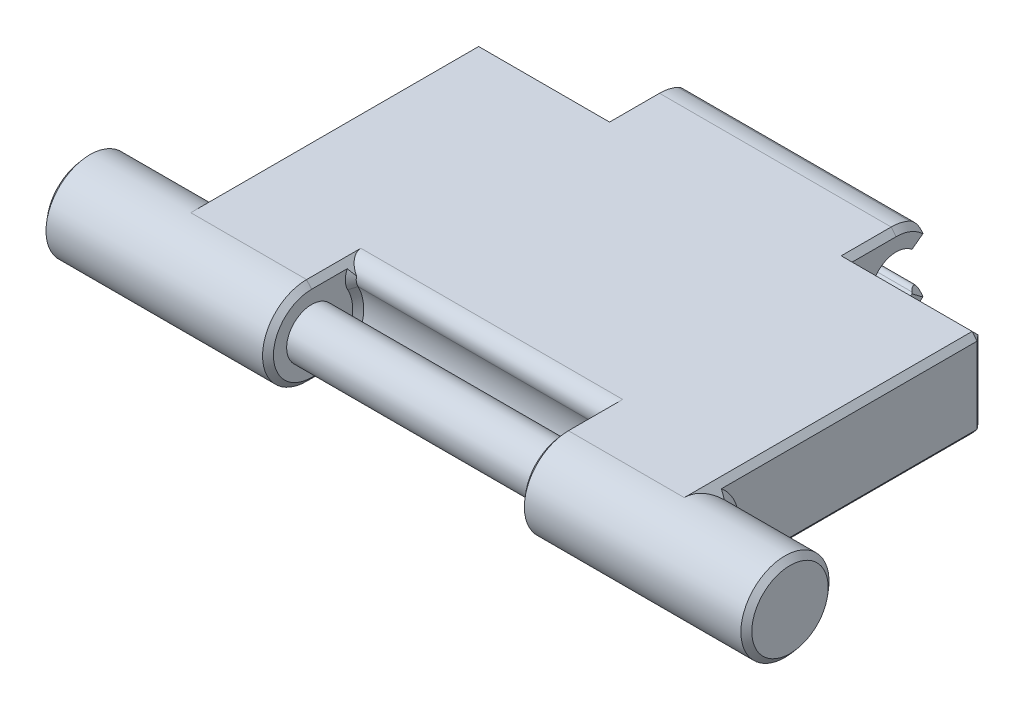
SolidWorks part; units mm, degrees
other "Markup1"
sketch "Sketch10" plane through (-10.5, 2.0625, -6.5697) normal (-0.116, 0.9645, -0.2372) x (-0.6238, 0.1151, 0.7731)
ref_plane "Front Plane" through (0, 0, 0) normal (0, 0, 1) x (1, 0, 0)
ref_plane "Top Plane" through (0, 0, 0) normal (0, 1, 0) x (1, 0, 0)
ref_plane "Right Plane" through (0, 0, 0) normal (1, 0, 0) x (0, 0, -1)
sketch "Sketch1" plane through (0, 0, 0) normal (0, 1, 0) x (1, 0, 0)
  line L1 (-5, 2.5) -> (5, 2.5)
  line L2 (-5, 2.5) -> (-5, -2.5)
  line L3 (-5, -2.5) -> (5, -2.5)
  line L4 (5, 2.5) -> (5, -2.5)
  line L5 (-5, 2.5) -> (5, -2.5) construction
  line L6 (-5, -2.5) -> (5, 2.5) construction
  point P0 (0, 0)
extrude "Boss-Extrude1" add sketch "Sketch1" along normal blind 1.5
sketch "Sketch4" plane through (0, 0, 0) normal (1, 0, 0) x (0, 0, -1)
  line L0 (-2.5, 1.5) -> (-2.5, 0) construction
  circle A0 centre (-2.5, 0.75) radius 0.75
extrude "Boss-Extrude3" add sketch "Sketch4" along normal mid plane 14
sketch "Sketch5" plane through (0, 0, 0) normal (1, 0, 0) x (0, 0, -1)
  circle A0 centre (-2.5, 0.75) radius 0.425
  circle A2 centre (-2.5, 0.75) radius 0.8
  dimension "D1" = 1.6
  dimension "D2" = 0.85
extrude "Cut-Extrude1" cut sketch "Sketch5" against normal mid plane 5
fillet "Fillet1" radius 0.25 2 edges at (0, 1.5, 2.2216) (0, 0, 2.2216)
sketch "Sketch8" plane through (0, 0, 0) normal (1, 0, 0) x (0, 0, -1)
  line L12 (3.25, 1.5) -> (2.5, 1.5)
  line L13 (2.5, 1.5) -> (2.5, 0)
  line L14 (2.5, 0) -> (3.25, 0)
  line L15 (3.5897, 1.0054) -> (3.8495, 1.2007)
  line L17 (3.8495, 0.2993) -> (3.5897, 0.4946)
  arc A4 (3.5897, 1.0054) -> (3.5897, 0.4946) centre (3.25, 0.75) ccw
  arc A12 (3.25, 0) -> (3.8495, 0.2993) centre (3.25, 0.75) ccw
  arc A13 (3.8495, 1.2007) -> (3.25, 1.5) centre (3.25, 0.75) ccw
extrude "Boss-Extrude5" add sketch "Sketch8" along normal mid plane 4.8
chamfer "Chamfer2" distance 0.1 angle 45 28 edges at (2.5, 0, 2.0383) (-2.5, 0, 2.0383) (2.5, 0.75, 3.25) (2.5, 1.5, 2.0383) (-2.5, 0.75, 3.25) (-2.5, 1.5, 2.0383) (5, 0, 0) (2.4, 0, -2.875) (3.7, 0, -2.5) (2.4, 1.5, -2.875) (3.7, 1.5, -2.5) (5, 1.5, 0) (5, 0.75, -2.5) (-2.4, 0, -2.875) (-3.7, 0, -2.5) (-5, 0, 0) (-5, 1.5, 0) (-2.4, 1.5, -2.875) (-3.7, 1.5, -2.5) (-5, 0.75, -2.5) (2.4, 0.079, -3.585) (2.4, 1.421, -3.585) (-2.4, 0.079, -3.585) (-2.4, 1.421, -3.585) (-2.4, 0.397, -3.7196) (-2.4, 1.103, -3.7196) (2.4, 0.397, -3.7196) (2.4, 1.103, -3.7196)
chamfer "Chamfer3" distance 0.1 angle 45 10 edges at (-2.5, 0.2316, 1.826) (-2.5, 1.2684, 1.826) (-2.5, 0.75, 1.7) (2.5, 0.2316, 1.826) (2.5, 1.2684, 1.826) (2.5, 0.75, 1.7) (-7, 0.75, 1.75) (7, 0.75, 1.75) (5, 0.75, 1.75) (-5, 0.75, 1.75)
fillet "Fillet3" radius 0.1 2 edges at (0, 0.4946, -3.5897) (0, 1.0054, -3.5897)
fillet "Fillet4" radius 0.25 2 edges at (0, 0.2993, -3.8495) (0, 1.2007, -3.8495)
scale "Scale1" scale about centroid uniform scaling no x scale factor 1.5 y scale factor 1.75 z scale factor 1.75
